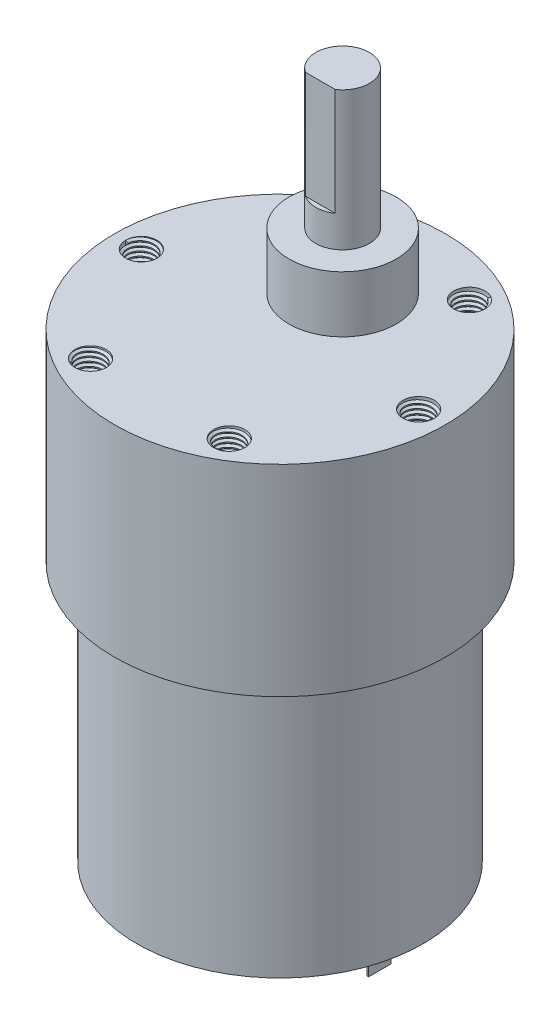
SolidWorks part; units mm, degrees
ref_plane "Front Plane" through (0, 0, 0) normal (0, 0, 1) x (1, 0, 0)
ref_plane "Top Plane" through (0, 0, 0) normal (0, 1, 0) x (1, 0, 0)
ref_plane "Right Plane" through (0, 0, 0) normal (1, 0, 0) x (0, 0, -1)
sketch "Sketch1" plane through (0, 0, 0) normal (0, 1, 0) x (1, 0, 0)
  line L0 (-16, 0) -> (16, 0) construction
  line L1 (0, 16) -> (0, -16) construction
  circle A0 centre (0, 0) radius 16
  dimension "D1" = 32
extrude "Boss-Extrude1" add sketch "Sketch1" along normal blind 29
sketch "Sketch2" plane through (0, 29, 0) normal (0, 1, 0) x (1, 0, 0)
  circle A0 centre (0, 0) radius 18.5
  circle A1 centre (0, 0) radius 16
  circle A2 centre (0, 0) radius 16
  circle M2 centre (0, 0) radius 16
  dimension "D2" = 37
  dimension "D1" = 0
extrude "Boss-Extrude2" add sketch "Sketch2" along normal blind 22.5 contours M2 | A0 M2 region at (-17.9767, 29, 0) region at (0, 29, 0)
sketch "Sketch3" plane through (0, 51.5, 0) normal (0, 1, 0) x (1, 0, 0)
  line L0 (-15.5, 0) -> (15.5, 0) construction
  line L1 (0, 15.5) -> (0, -15.5) construction
  circle A0 centre (0, 0) radius 15.5
  circle A1 centre (0, 0) radius 18.5
  circle A2 centre (0, 0) radius 18.5
  circle A3 centre (0, 7) radius 6
  point P12 (0, 1)
  dimension "D2" = 31
  dimension "D3" = 12
  dimension "D4" = 7
  dimension "D1" = 0
extrude "Boss-Extrude3" add sketch "Sketch3" along normal blind 6.3 contours A3 region at (0, 51.5, -7)
sketch "Sketch4" plane through (0, 57.8, 0) normal (0, 1, 0) x (1, 0, 0)
  line L0 (-18.5, 0) -> (18.5, 0) construction
  line L1 (0, 18.5) -> (0, -18.5) construction
  line L2 (-1.6583, 4.5) -> (1.6583, 4.5)
  circle A0 centre (0, 7) radius 6 construction
  circle A1 centre (0, 0) radius 18.5 construction
  circle A2 centre (0, 7) radius 6
  circle A3 centre (0, 0) radius 18.5
  circle A4 centre (0, 7) radius 3
  point P13 (0, 4)
  point P14 (0, 10)
  dimension "D1" = 6
  dimension "D2" = 5.5
extrude "Boss-Extrude4" add sketch "Sketch4" along normal blind 3.5 contours L2 A4 | L2 A4 region at (0, 57.8, -7.112) region at (0, 57.8, -4.2985)
extrude "Boss-Extrude5" add sketch "Sketch4<3>" along normal blind 12 from surface contours L2 A4 region at (0, 57.8, -7.112) starting at face at (0, 61.3, -4)
sketch "Sketch4<3>" plane through (0, 57.8, 0) normal (0, 1, 0) x (1, 0, 0) same geometry as "Sketch4"
sketch "Sketch5" plane through (0, 51.5, 0) normal (0, 1, 0) x (1, 0, 0)
  circle A0 centre (0, 0) radius 15.5
  circle A1 centre (0, 0) radius 18.5
  circle A2 centre (0, 0) radius 18.5
  circle A3 centre (-15.5, 0) radius 1.75
  dimension "D2" = 31
  dimension "D3" = 3.5
  dimension "D1" = 0
extrude "Cut-Extrude2" cut sketch "Sketch5" against normal blind 3.5 contours A0 A3 | A0 A3 region at (-14.7398, 51.5, 0) region at (-16.2246, 51.5, 0)
thread "Thread1" pitch 0.5 method extrude profile "Thread Profile2" start angle 0, offset 0, length 0, pitch 0.5, diameter 3.5
ref_plane "Plane2" through (-17.25, 51.5, 0) normal (0, 0, 1) x (-1, 0, 0)
sketch "Thread Profile2" plane through (-17.25, 51.5, 0) normal (0, 0, 1) x (-1, 0, 0)
  line L0 (0, 0) -> (0, 0.5) construction
  line L11 (0, 0) -> (0, 0.4375)
  line L12 (0, 0.4375) -> (-0.2706, 0.2812)
  line L13 (-0.2706, 0.2812) -> (-0.2706, 0.1562)
  line L15 (-0.2706, 0.1562) -> (0, 0)
  line L17 (-0.2706, 0.2187) -> (0, 0.2187) construction
  point P2 (0, 0)
  dimension "Pitch" = 0.5
  dimension "Profile_Angle" = 60
  dimension "Profile_Land" = 0.125
  dimension "Profile_Height" = 0.2706
pattern_circular "CirPattern1" count 6 every 60 about axis through (0, 51.5, 0) along (0, 1, 0) of "Cut-Extrude2", "Thread1"
sketch "Sketch12" plane through (0, 0, 0) normal (0, -1, 0) x (1, 0, 0)
  line L0 (-16, 0) -> (16, 0) construction
  line L1 (-11.15, 1.25) -> (-11, 1.25)
  line L2 (-11.15, 1.25) -> (-11.15, -1.25)
  line L3 (-11.15, -1.25) -> (-11, -1.25)
  line L4 (-11, 1.25) -> (-11, -1.25)
  line L5 (0, 16) -> (0, -16) construction
  line L10 (11, 1.25) -> (11.15, 1.25)
  line L11 (11, 1.25) -> (11, -1.25)
  line L12 (11, -1.25) -> (11.15, -1.25)
  line L13 (11.15, 1.25) -> (11.15, -1.25)
  circle A1 centre (0, 0) radius 16
  circle A2 centre (0, 0) radius 16
  point P9 (-11.15, 0)
  point P14 (11.15, 0)
  dimension "D2" = 2.5
  dimension "D3" = 0.15
  dimension "D4" = 22
  dimension "D1" = 0
extrude "Boss-Extrude6" add sketch "Sketch12" along normal blind 5 contours L2 L3 L4 L1 | L11 L12 L13 L10
equation "\"D1@Boss-Extrude4\"=15.5-12mm"
